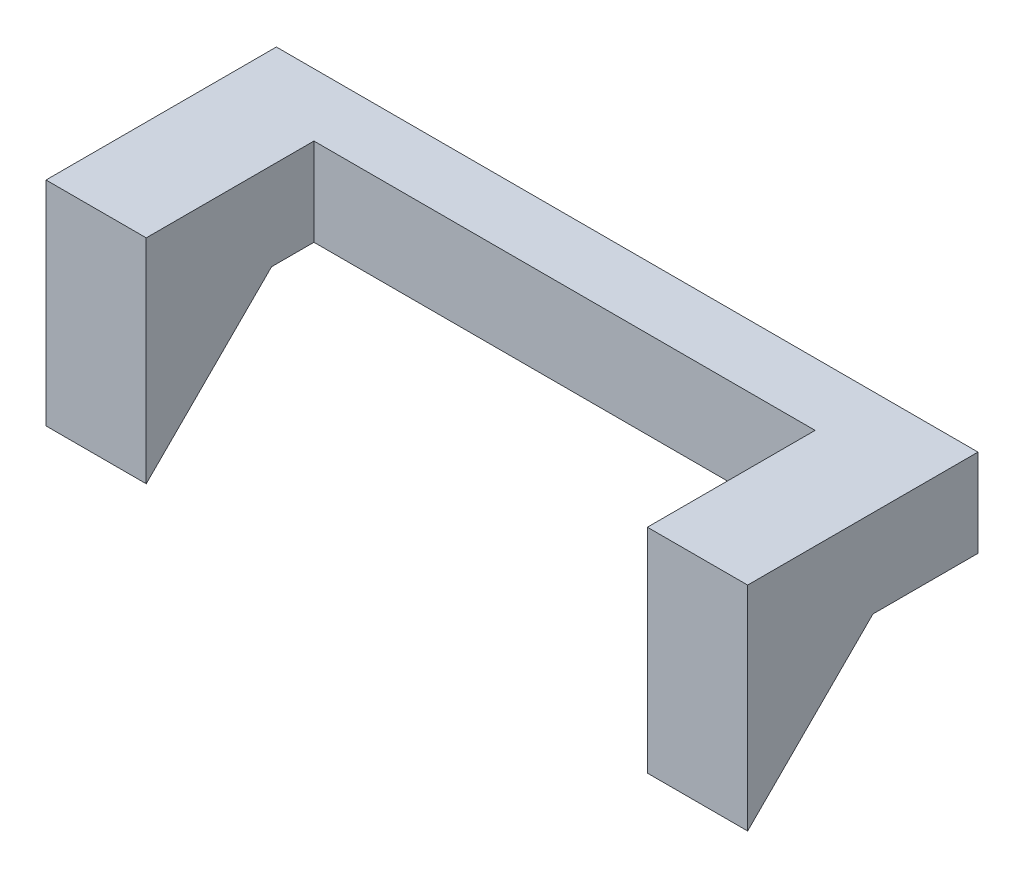
SolidWorks part; units mm, degrees
material "ABS"
ref_plane "Front Plane" through (0, 0, 0) normal (0, 0, 1) x (1, 0, 0)
ref_plane "Top Plane" through (0, 0, 0) normal (0, 1, 0) x (1, 0, 0)
ref_plane "Right Plane" through (0, 0, 0) normal (1, 0, 0) x (0, 0, -1)
sketch "Sketch1" plane through (0, 0, 0) normal (0, 0, 1) x (1, 0, 0)
  line L0 (194.8759, -18.266) -> (194.8759, 12.7177) construction
  line L1 (110.9437, 6.0204) -> (115.5497, 27.6896) construction
  line L2 (115.5497, 27.6896) -> (77.4118, 35.7961) construction
  line L3 (77.4118, 35.7961) -> (72.8059, 14.1269) construction
  line L4 (72.8059, 14.1269) -> (110.9437, 6.0204) construction
  line L26 (106.941, 56.2537) -> (178.061, 56.2537)
  line L27 (106.941, 56.2537) -> (106.941, 65.1437)
  line L28 (106.941, 65.1437) -> (178.061, 65.1437)
  line L29 (178.061, 56.2537) -> (178.061, 65.1437)
  circle A0 centre (118.0651, 15.8308) radius 1.7444 construction
  circle A1 centre (70.2904, 25.9857) radius 1.7444 construction
  spline S0 degree 3 poles (194.8759, 12.7177) (183.825, 15.5844) (147.8627, 24.5589) (89.5348, 38.165) (16.5232, 51.8472) (-56.3965, 54.2997) (-121.7864, 41.7027) (-166.8334, 20.6064) (-197.5997, -0.5327) (-211.2728, -18.844) (-212.6858, -31.6808) knots 0.249366 0.249366 0.249366 0.249366 0.308456 0.442388 0.551518 0.687091 0.811391 0.886312 0.939136 1 1 1 1 construction
  spline S1 degree 3 poles (-212.6858, -31.6808) (-210.54, -43.7591) (-185.9692, -42.477) (-149.0968, -42.319) (-96.6762, -32.7044) (-19.94, -20.8983) (62.4309, -15.9284) (137.9968, -16.2355) (178.2787, -17.3378) (194.8759, -18.266) knots 0 0 0 0 0.056908 0.106483 0.214488 0.341298 0.535096 0.664681 0.755789 0.755789 0.755789 0.755789 construction
  dimension "D1" = 71.12
  dimension "D2" = 8.89
extrude "Boss-Extrude1" add sketch "Sketch1" along normal blind 6.35
sketch "Sketch5" plane through (0, 0, 6.35) normal (0, 0, 1) x (1, 0, 0)
  line L0 (178.061, 65.1437) -> (106.941, 65.1437) construction
  line L1 (106.941, 56.2537) -> (117.101, 56.2537)
  line L2 (106.941, 56.2537) -> (106.941, 65.1437)
  line L3 (106.941, 65.1437) -> (117.101, 65.1437)
  line L4 (117.101, 56.2537) -> (117.101, 65.1437)
  line L6 (178.061, 56.2537) -> (167.901, 56.2537)
  line L7 (178.061, 56.2537) -> (178.061, 65.1437)
  line L8 (178.061, 65.1437) -> (167.901, 65.1437)
  line L9 (167.901, 56.2537) -> (167.901, 65.1437)
  dimension "D1" = 10.16
extrude "Boss-Extrude5" add sketch "Sketch5" along normal blind 17
sketch "Sketch6" plane through (0, 56.2537, 0) normal (0, -1, 0) x (1, 0, 0)
  line L0 (167.901, 23.35) -> (167.901, 6.35) construction
  line L1 (178.061, 23.35) -> (167.901, 23.35)
  line L2 (178.061, 23.35) -> (178.061, 10.65)
  line L3 (178.061, 10.65) -> (167.901, 10.65)
  line L4 (167.901, 23.35) -> (167.901, 10.65)
  line L6 (117.101, 23.35) -> (106.941, 23.35)
  line L7 (117.101, 23.35) -> (117.101, 10.65)
  line L8 (117.101, 10.65) -> (106.941, 10.65)
  line L9 (106.941, 23.35) -> (106.941, 10.65)
  line L10 (106.941, 23.35) -> (106.941, 0) construction
  dimension "D1" = 12.7
extrude "Boss-Extrude6" add sketch "Sketch6" along normal blind 12.7
chamfer "Chamfer3" distance 12.7 angle 45 2 edges at (112.021, 43.5537, 10.65) (172.981, 43.5537, 10.65)
